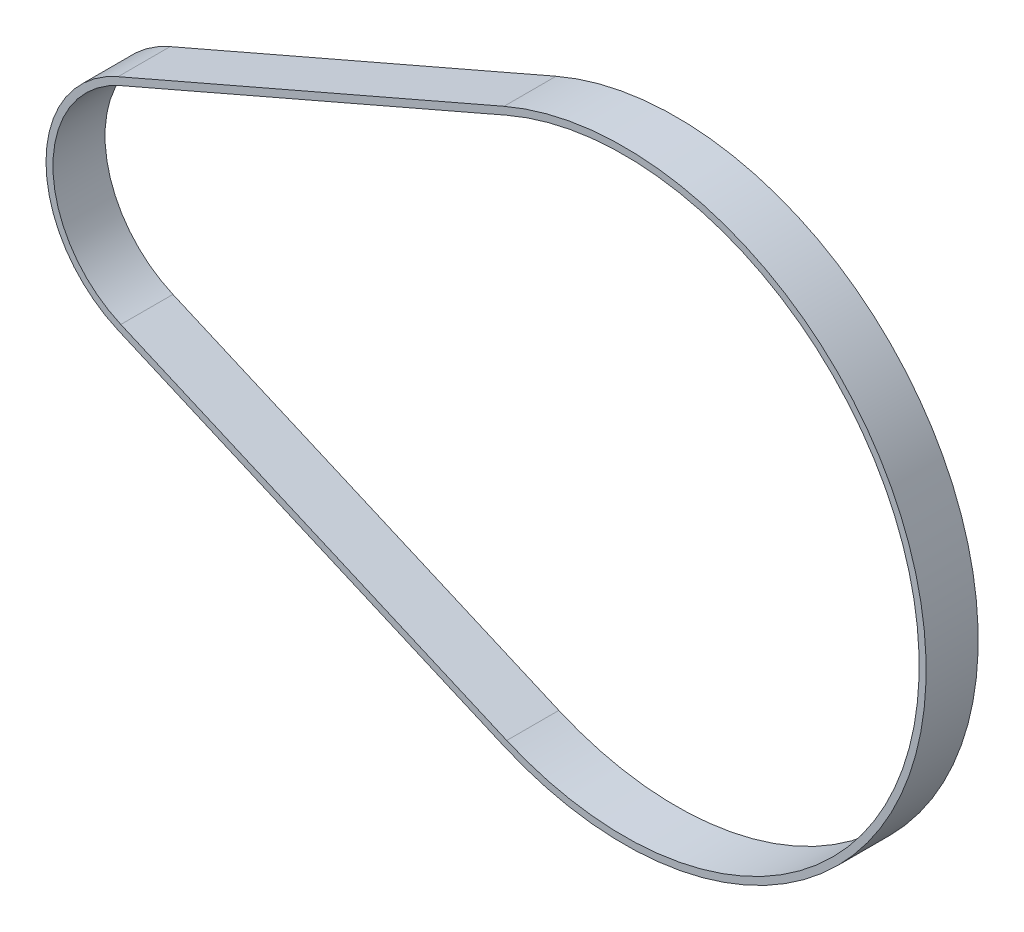
SolidWorks part; units mm, degrees
ref_plane "前视基准面" through (0, 0, 0) normal (0, 0, 1) x (1, 0, 0)
ref_plane "上视基准面" through (0, 0, 0) normal (0, 1, 0) x (1, 0, 0)
ref_plane "右视基准面" through (0, 0, 0) normal (1, 0, 0) x (0, 0, -1)
sketch "草图1" plane through (0, 0, 0) normal (0, 0, 1) x (1, 0, 0)
  line L0 (-5.484, -12.6505) -> (38.9802, -31.9257)
  line L1 (38.9802, 31.9257) -> (-5.484, 12.6505)
  line L2 (-5.1658, -11.9165) -> (39.2984, -31.1917)
  line L3 (39.2984, 31.1917) -> (-5.1658, 11.9165)
  arc A0 (-5.484, 12.6505) -> (-5.484, -12.6505) centre (0, 0) ccw
  arc A1 (38.9802, -31.9257) -> (38.9802, 31.9257) centre (52.82, 0) ccw
  arc A2 (-5.1658, 11.9165) -> (-5.1658, -11.9165) centre (0, 0) ccw
  arc A3 (39.2984, -31.1917) -> (39.2984, 31.1917) centre (52.82, 0) ccw
extrude "凸台-拉伸1" add sketch "草图1" against normal blind 3 and the other way blind 3
ref_plane "C1 XY" through (0, 0, 0) normal (0, 0, 1) x (1, 0, 0)
ref_plane "C1 XZ" through (0, 0, 0) normal (0, -1, 0) x (-1, 0, 0)
ref_plane "C1 YZ" through (0, 0, 0) normal (1, 0, 0) x (0, 0, -1)
ref_axis "C1 X" through (-80.9, 0, 0) along (1, 0, 0)
ref_axis "C1 Y" through (0, -50, 0) along (0, 1, 0)
ref_axis "C1 Z" through (0, 0, 80.9) along (0, 0, -1)
sketch3d "C1"
  point P0 (0, 0, 0)
ref_plane "C2 XY" through (0, 0, 0) normal (0, 0, 1) x (1, 0, 0)
ref_plane "C2 XZ" through (0, 0, 0) normal (0, -1, 0) x (-1, 0, 0)
ref_plane "C2 YZ" through (52.82, 0, 0) normal (1, 0, 0) x (0, 0, -1)
ref_axis "C2 X" through (-80.9, 0, 0) along (1, 0, 0)
ref_axis "C2 Y" through (52.82, -50, 0) along (0, 1, 0)
ref_axis "C2 Z" through (52.82, 0, 80.9) along (0, 0, -1)
sketch3d "C2"
  point P0 (52.82, 0, 0)
other "冻结***"
